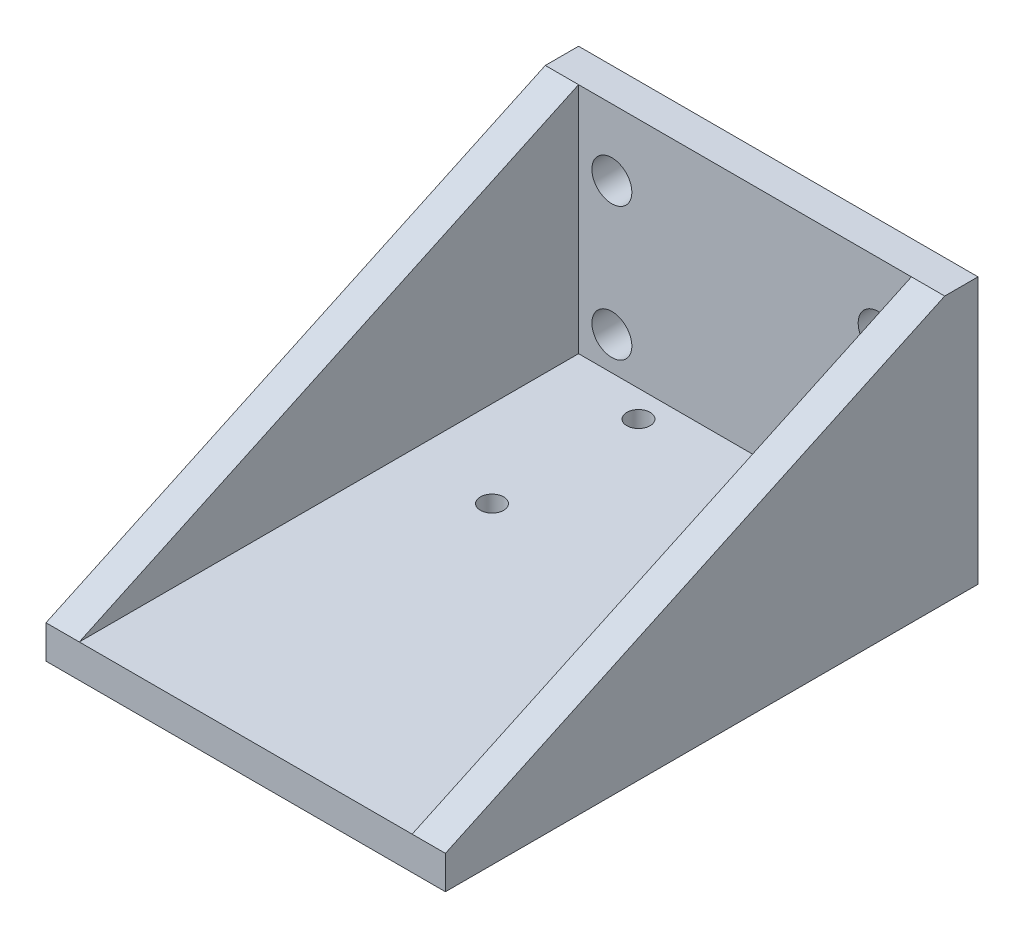
SolidWorks part; units mm, degrees
ref_plane "Спереди" through (0, 0, 0) normal (0, 0, 1) x (1, 0, 0)
ref_plane "Сверху" through (0, 0, 0) normal (0, 1, 0) x (1, 0, 0)
ref_plane "Справа" through (0, 0, 0) normal (1, 0, 0) x (0, 0, -1)
sketch "Эскиз1" plane through (0, 0, 0) normal (0, 1, 0) x (1, 0, 0)
  line L1 (0, 0) -> (60, 0)
  line L2 (0, 0) -> (0, 80)
  line L3 (0, 80) -> (60, 80)
  line L4 (60, 0) -> (60, 80)
  dimension "D1" = 80
  dimension "D2" = 60
extrude "Бобышка-Вытянуть1" add sketch "Эскиз1" along normal blind 5
sketch "Эскиз3" plane through (0, 5, 0) normal (0, 1, 0) x (1, 0, 0)
  line L0 (5, 75) -> (55, 75)
  line L1 (55, 75) -> (55, 0)
  line L2 (0, 0) -> (60, 0) construction
  line L3 (55, 0) -> (60, 0)
  line L4 (60, 0) -> (60, 80)
  line L5 (60, 80) -> (0, 80)
  line L6 (0, 80) -> (0, 0)
  line L7 (0, 0) -> (5, 0)
  line L8 (5, 0) -> (5, 75)
  dimension "D1" = 5
  dimension "D2" = 5
  dimension "D3" = 5
  dimension "D4" = 75
extrude "Бобышка-Вытянуть2" add sketch "Эскиз3" along normal blind 35
sketch "Эскиз4" plane through (0, 0, -80) normal (0, 0, -1) x (-1, 0, 0)
  line L0 (-30, 0) -> (-30, 40) construction
  line L1 (-60, 0) -> (0, 0) construction
  line L2 (-60, 40) -> (0, 40) construction
  line L3 (0, 10) -> (-60, 10) construction
  line L4 (0, 40) -> (0, 0) construction
  line L5 (-60, 40) -> (-60, 0) construction
  line L6 (-60, 30) -> (0, 30) construction
  line L7 (-60, 40) -> (-60, 0) construction
  circle A0 centre (-10, 10) radius 3
  circle A1 centre (-10, 30) radius 3
  circle A2 centre (-50, 30) radius 3
  circle A3 centre (-50, 10) radius 3
  dimension "D3" = 6
  dimension "D1" = 10
  dimension "D2" = 10
  dimension "D4" = 10
  dimension "D5" = 10
extrude "Вырез-Вытянуть1" cut sketch "Эскиз4" against normal up to surface (5 mm away) up to face at (30, 22.5, -75)
sketch "Эскиз5" plane through (0, 0, 0) normal (0, -1, 0) x (-1, 0, 0)
  line L0 (-30, 80) -> (-30, 0) construction
  line L1 (-60, 80) -> (0, 80) construction
  line L2 (0, 0) -> (-60, 0) construction
  line L3 (-42, 71) -> (-42, 49) construction
  line L4 (-42, 49) -> (-18, 49) construction
  line L5 (-18, 49) -> (-18, 71) construction
  line L6 (-18, 71) -> (-42, 71) construction
  circle A0 centre (-42, 71) radius 1.75
  circle A1 centre (-18, 71) radius 1.75
  circle A2 centre (-18, 49) radius 1.75
  circle A3 centre (-42, 49) radius 1.75
  point P8 (-30, 71)
  dimension "D3" = 3.5
  dimension "D1" = 22
  dimension "D2" = 24
  dimension "D4" = 9
extrude "Вырез-Вытянуть2" cut sketch "Эскиз5" against normal up to surface (5 mm away) up to face at (30, 5, -37.5)
sketch "Эскиз6" plane through (60, 0, 0) normal (1, 0, 0) x (0, 0, -1)
  line L0 (75, 40) -> (0, 5)
  line L1 (0, 40) -> (80, 40) construction
  line L2 (0, 40) -> (0, 0) construction
  line L3 (75, 40) -> (0, 40)
  line L4 (0, 40) -> (0, 5)
  line L5 (80, 40) -> (80, 0) construction
  line L6 (0, 0) -> (80, 0) construction
  dimension "D1" = 5
  dimension "D2" = 5
extrude "Вырез-Вытянуть3" cut sketch "Эскиз6" against normal up to surface (60 mm away) up to face at (0, 20, -40)
